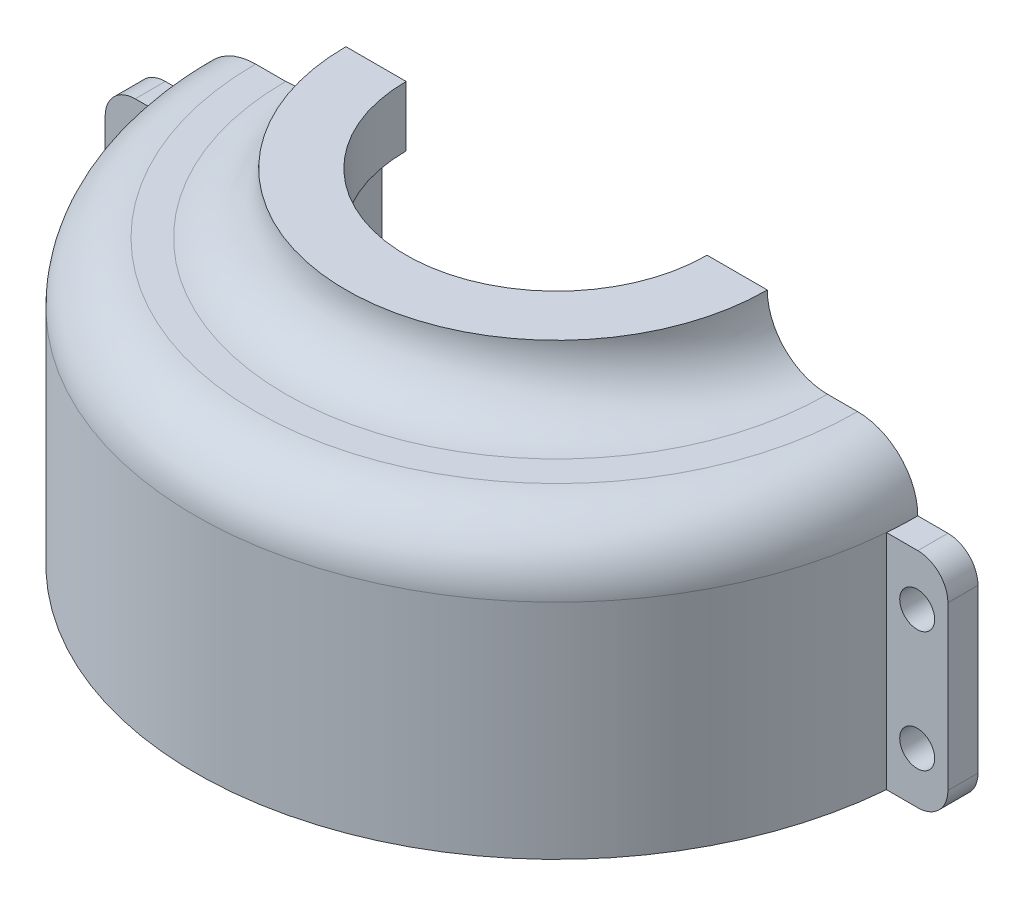
SolidWorks part; units mm, degrees
ref_plane "Front Plane" through (0, 0, 0) normal (0, 0, 1) x (1, 0, 0)
ref_plane "Top Plane" through (0, 0, 0) normal (0, 1, 0) x (1, 0, 0)
ref_plane "Right Plane" through (0, 0, 0) normal (1, 0, 0) x (0, 0, -1)
sketch "Sketch1" plane through (0, 0, 0) normal (0, 1, 0) x (1, 0, 0)
  circle A0 centre (0, 0) radius 20
  circle A1 centre (0, 0) radius 25
  dimension "D1" = 40
  dimension "D2" = 5
extrude "Boss-Extrude1" add sketch "Sketch1" along normal blind 5
sketch "Sketch2" plane through (0, 5, 0) normal (0, 1, 0) x (1, 0, 0)
  line L5 (31.7809, -26.6264) -> (-31.7809, 26.6264) construction
  line L6 (31.7809, 26.6264) -> (-31.7809, -26.6264) construction
  circle A0 centre (0, 0) radius 20
  circle A1 centre (0, 0) radius 60
  point P0 (0, 0)
  dimension "D1" = 120
extrude "Boss-Extrude2" add sketch "Sketch2" against normal blind 5
sketch "Sketch3" plane through (0, 5, 0) normal (0, 1, 0) x (1, 0, 0)
  circle A0 centre (0, 0) radius 55
  circle A1 centre (0, 0) radius 60 construction
  circle A2 centre (0, 0) radius 60
  dimension "D1" = 5
extrude "Boss-Extrude3" add sketch "Sketch3" along normal blind 17
sketch "Sketch4" plane through (0, 22, 0) normal (0, 1, 0) x (1, 0, 0)
  circle A0 centre (0, 0) radius 60
  circle A1 centre (0, 0) radius 29
  dimension "D1" = 58
extrude "Boss-Extrude4" add sketch "Sketch4" along normal blind 25
sketch "Sketch5" plane through (0, 47, 0) normal (0, 1, 0) x (1, 0, 0)
  circle A0 centre (0, 0) radius 25
  circle A1 centre (0, 0) radius 35
  dimension "D1" = 50
  dimension "D2" = 10
extrude "Boss-Extrude5" add sketch "Sketch5" along normal blind 10
fillet "Fillet2" radius 10 2 edges at (0, 47, 35) (0, 47, 60)
sketch "Sketch6" plane through (0, 0, 0) normal (0, 0, 1) x (1, 0, 0)
  line L0 (-60, 0) -> (60, 0) construction
  line L1 (-60, 37) -> (-70, 37)
  line L2 (-60, 37) -> (-60, 0)
  line L3 (-60, 0) -> (-70, 0)
  line L4 (-70, 37) -> (-70, 0)
  line L10 (-52.9229, 5.4073) -> (-70, 37) construction
  line L11 (-48.3607, 40.0328) -> (-70, 0) construction
  point P7 (-60, 18.5)
  dimension "D1" = 0
  dimension "D2" = 10
extrude "Boss-Extrude7" add sketch "Sketch6" along normal mid plane 10 separate body
sketch "Sketch7" plane through (-70, 0, 0) normal (-1, 0, 0) x (0, 0, 1)
  line L1 (5, 37) -> (-5, 37)
  line L2 (5, 37) -> (5, 0)
  line L3 (5, 0) -> (-5, 0)
  line L4 (-5, 37) -> (-5, 0)
extrude "Boss-Extrude8" add sketch "Sketch7" against normal up to surface (10.2087 mm away) up to face at (0, 37, 60)
sketch "Sketch8" plane through (0, 0, 5) normal (0, 0, 1) x (1, 0, 0)
  line L0 (-64.8957, 8.5) -> (-64.8957, 28.5)
  line L1 (-59.7913, 37) -> (-70, 37) construction
  line L2 (-70, 0) -> (-70, 37) construction
  point P3 (-64.8957, 18.5)
  point P5 (-64.8957, 37)
  point P8 (-70, 18.5)
  dimension "D1" = 0
  dimension "D2" = 0
  dimension "D3" = 20
hole_wizard "M5 Clearance Hole1" positions "Sketch9" profile "Sketch10" hole size "M5" standard "ANSI Metric" end condition through all
sketch "Sketch9" plane through (0, 0, 5) normal (0, 0, 1) x (1, 0, 0)
  point P0 (-64.8957, 8.5)
  point P3 (-64.8957, 28.5)
sketch "Sketch10" plane through (-64.8957, 8.5, 5) normal (1, 0, 0) x (0, -1, 0)
  line L0 (0, 0) -> (0, 65)
  line L1 (0, 65) -> (2.9, 65)
  line L2 (2.9, 65) -> (2.9, 0)
  line L5 (2.9, 0) -> (0, 0)
  line L11 (0, -6.35) -> (0, 107.95) construction
  dimension "Thru Hole Dia." = 5.8
  dimension "Thru Hole Depth" = 65
fillet "Fillet3" radius 5 2 edges at (-70, 0, 0) (-70, 37, 0)
mirror "Mirror1" about plane through (0, 0, 0) normal (1, 0, 0) of bodies 109
split "Split1" trim tools "Front Plane" bodies to split 110 resulting bodies 111 112
delete or keep bodies "Body-Delete/Keep 1" type delete bodies bodies 112
